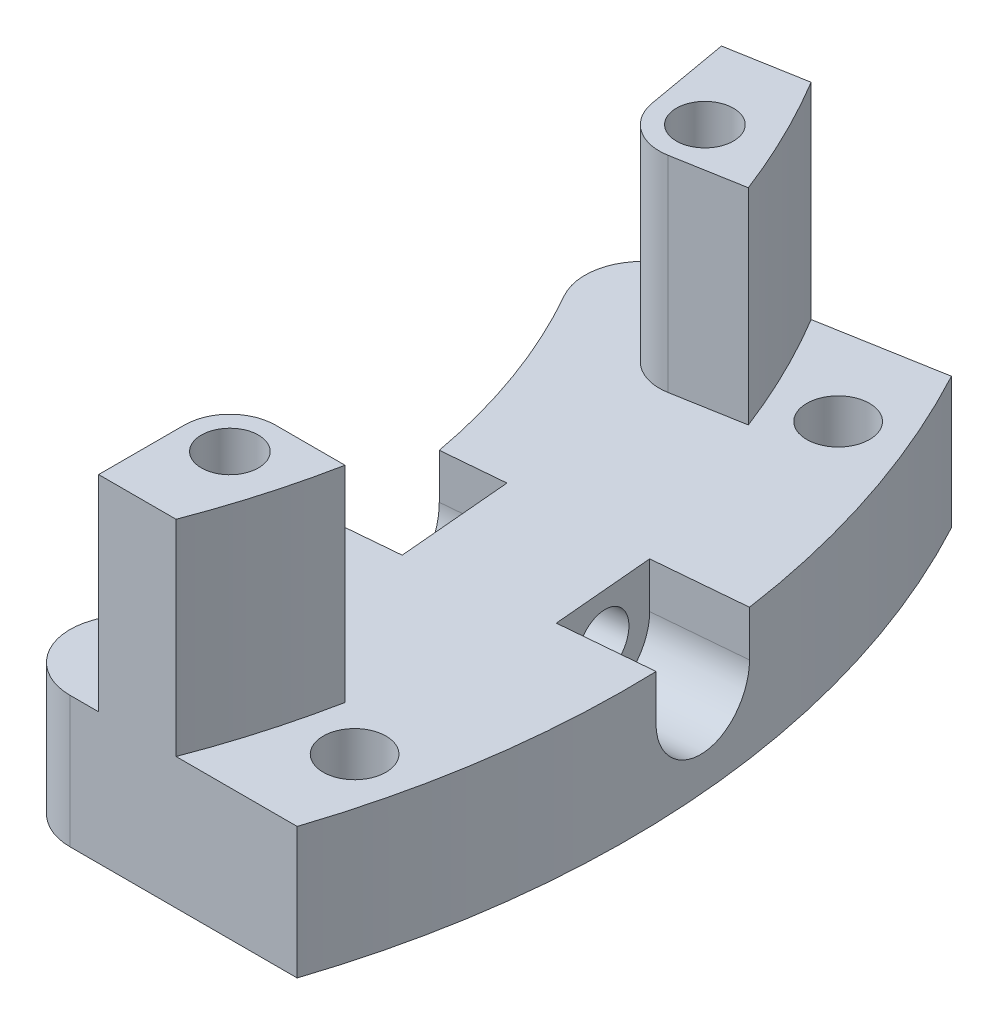
SolidWorks part; units mm, degrees
ref_plane "Front Plane" through (0, 0, 0) normal (0, 0, 1) x (1, 0, 0)
ref_plane "Top Plane" through (0, 0, 0) normal (0, 1, 0) x (1, 0, 0)
ref_plane "Right Plane" through (0, 0, 0) normal (1, 0, 0) x (0, 0, -1)
sketch "Sketch1" plane through (0, 0, 0) normal (0, 1, 0) x (1, 0, 0)
  line L0 (48.4934, -25) -> (75.9934, -25)
  line L1 (43.4155, 33.041) -> (70.4977, 37.8163)
  line L2 (0, -25) -> (48.4934, -25) construction
  line L3 (11.1696, 27.3552) -> (43.4155, 33.041) construction
  line L4 (-4.3412, 24.6202) -> (70.4977, 37.8163) construction
  arc A0 (70.4977, 37.8163) -> (75.9934, -25) centre (0, 0) cw
  arc A1 (43.4155, 33.041) -> (48.4934, -25) centre (0, 0) cw
  circle A2 centre (0, 0) radius 25 construction
  arc A3 (-4.3412, 24.6202) -> (0, -25) centre (0, 0) ccw construction
  dimension "D1" = 80
  dimension "D3" = 27.5
  dimension "D4" = 50
extrude "Boss-Extrude1" add sketch "Sketch1" along normal blind 11.5
sketch "Sketch2" plane through (0, 11.5, 0) normal (0, -1, 0) x (1, 0, 0)
  line L0 (48.4934, 25) -> (75.9934, 25) construction
  line L1 (70.4977, -37.8163) -> (43.4155, -33.041) construction
  line L2 (70.4977, -37.8163) -> (43.4155, -33.041) construction
  line L3 (62.5999, 13.5) -> (68.6859, 13.5)
  line L4 (58.5999, 17.5) -> (58.5999, 25)
  line L5 (48.4934, 25) -> (75.9934, 25) construction
  line L6 (58.5999, 25) -> (65.3835, 25)
  line L7 (54.6708, -27.4099) -> (53.3685, -34.796)
  line L8 (59.3046, -24.1653) -> (65.2981, -25.2221)
  line L9 (60.049, -35.9739) -> (53.3685, -34.796)
  arc A0 (65.3835, 25) -> (60.049, -35.9739) centre (0, 0) cw construction
  arc A1 (70.4977, -37.8163) -> (75.9934, 25) centre (0, 0) ccw construction
  arc A2 (58.5999, 17.5) -> (62.5999, 13.5) centre (62.5999, 17.5) ccw
  circle A3 centre (62.5999, 17.5) radius 5 construction
  arc A4 (59.3046, -24.1653) -> (54.6708, -27.4099) centre (58.61, -28.1045) ccw
  circle A5 centre (58.61, -28.1045) radius 5 construction
  arc A6 (65.3835, 25) -> (68.6859, 13.5) centre (0, 0) cw
  arc A7 (60.049, -35.9739) -> (65.2981, -25.2221) centre (0, 0) ccw
  dimension "D1" = 10
  dimension "D2" = 10
  dimension "D4" = 8
  dimension "D5" = 7.5
  dimension "D3" = 7.5
sketch "Sketch4" plane through (0, 0, 0) normal (0, -1, 0) x (1, 0, 0)
  circle A0 centre (73.0264, 17) radius 4.5
  circle A1 centre (68.965, -29.4226) radius 4.5
  circle A2 centre (73.0264, 17) radius 3.3 construction
  circle A3 centre (68.965, -29.4226) radius 3.3 construction
  dimension "D1" = 9
extrude "Cut-Extrude2" cut sketch "Sketch4" against normal blind 5
sketch "Sketch5" plane through (0, 5, 0) normal (0, -1, 0) x (1, 0, 0)
  circle A0 centre (73.0264, 17) radius 2.75
  circle A1 centre (68.965, -29.4226) radius 2.75
  dimension "D1" = 5.5
extrude "Cut-Extrude3" cut sketch "Sketch5" against normal through all
ref_plane "Plane1" through (45.9545, 0, -4.0205) normal (-0.9962, 0, 0.0872) x (0.0872, 0, 0.9962)
sketch "Sketch6" plane through (45.9545, 0, -4.0205) normal (-0.9962, 0, 0.0872) x (0.0872, 0, 0.9962)
  line L1 (29.1313, 11.5) -> (-29.1313, 11.5) construction
  circle A0 centre (0, 7.5) radius 5 construction
  circle A1 centre (0, 7.5) radius 2.5
  circle A2 centre (0, 7.5) radius 4.5 construction
  dimension "D1" = 10
  dimension "D2" = 4
  dimension "D3" = 5
  dimension "D4" = 9
extrude "Cut-Extrude4" cut sketch "Sketch6" against normal through all
ref_plane "Plane2" through (79.6956, 0, -6.9725) normal (0.9962, 0, -0.0872) x (-0.0872, 0, -0.9962)
ref_plane "Plane3" through (62.825, 0, -5.4965) normal (0.9962, 0, -0.0872) x (-0.0872, 0, -0.9962)
sketch "Sketch8" plane through (79.6956, 0, -6.9725) normal (0.9962, 0, -0.0872) x (-0.0872, 0, -0.9962)
  line L0 (-4.5, 7.5) -> (-4.5, 11.5)
  line L1 (31.5281, 11.5) -> (-31.5281, 11.5) construction
  line L2 (4.5, 7.5) -> (4.5, 11.5)
  line L3 (4.5, 11.5) -> (-4.5, 11.5)
  arc A1 (-4.5, 7.5) -> (4.5, 7.5) centre (0, 7.5) ccw
  dimension "D1" = 9
extrude "Cut-Extrude5" cut sketch "Sketch8" against normal blind 8.2
sketch "Sketch7" plane through (0, 11.5, 0) normal (0, 1, 0) x (1, 0, 0)
  line L1 (51.1627, 9.5455) -> (52.043, -0.5161) construction
  line L2 (0, 0) -> (51.6029, 4.5147) construction
  line L3 (51.1627, 9.5455) -> (76.0676, 11.7243) construction
  line L4 (76.0676, 11.7243) -> (76.9479, 1.6628) construction
  line L5 (76.9479, 1.6628) -> (52.043, -0.5161) construction
  line L7 (71.1346, 10.7407) -> (71.919, 1.7749) construction
  line L10 (51.1627, 9.5455) -> (52.043, -0.5161)
  line L11 (52.043, -0.5161) -> (60.0126, 0.1811)
  line L12 (60.0126, 0.1811) -> (59.1323, 10.2427)
  line L13 (59.1323, 10.2427) -> (51.1627, 9.5455)
  line L14 (71.0866, 11.2886) -> (71.9669, 1.227) construction
  line L15 (71.919, 1.7749) -> (71.1346, 10.7407) construction
  line L16 (48.4934, -25) -> (75.9934, -25) construction
  line L17 (70.4977, 37.8163) -> (43.4155, 33.041) construction
  arc A1 (70.4977, 37.8163) -> (75.9934, -25) centre (0, 0) cw construction
  point P15 (71.5268, 6.2578)
  dimension "D3" = 8
  dimension "D5" = 80
  dimension "D1" = 10.1
  dimension "D2" = 25
  dimension "D4" = 5
extrude "Cut-Extrude6" cut sketch "Sketch7" against normal blind 9
fillet "Fillet1" radius 5.05 2 edges at (57.2851, 2.5, 0.0575) (56.4048, 2.5, -10.0041)
fillet "Fillet2" radius 5 2 edges at (48.4934, 5.75, 25) (43.4155, 5.75, -33.041)
extrude "Boss-Extrude2" add sketch "Sketch2" against normal offset from surface (18 mm away) 22
sketch "Sketch3" plane through (0, 29.5, 0) normal (0, 1, 0) x (1, 0, 0)
  circle A0 centre (58.61, 28.1045) radius 2.5
  circle A1 centre (62.5999, -17.5) radius 2.5
  arc A2 (54.6708, 27.4099) -> (59.3046, 24.1653) centre (58.61, 28.1045) ccw construction
  arc A3 (62.5999, -13.5) -> (58.5999, -17.5) centre (62.5999, -17.5) ccw construction
  dimension "D1" = 5
extrude "Cut-Extrude1" cut sketch "Sketch3" against normal blind 4
